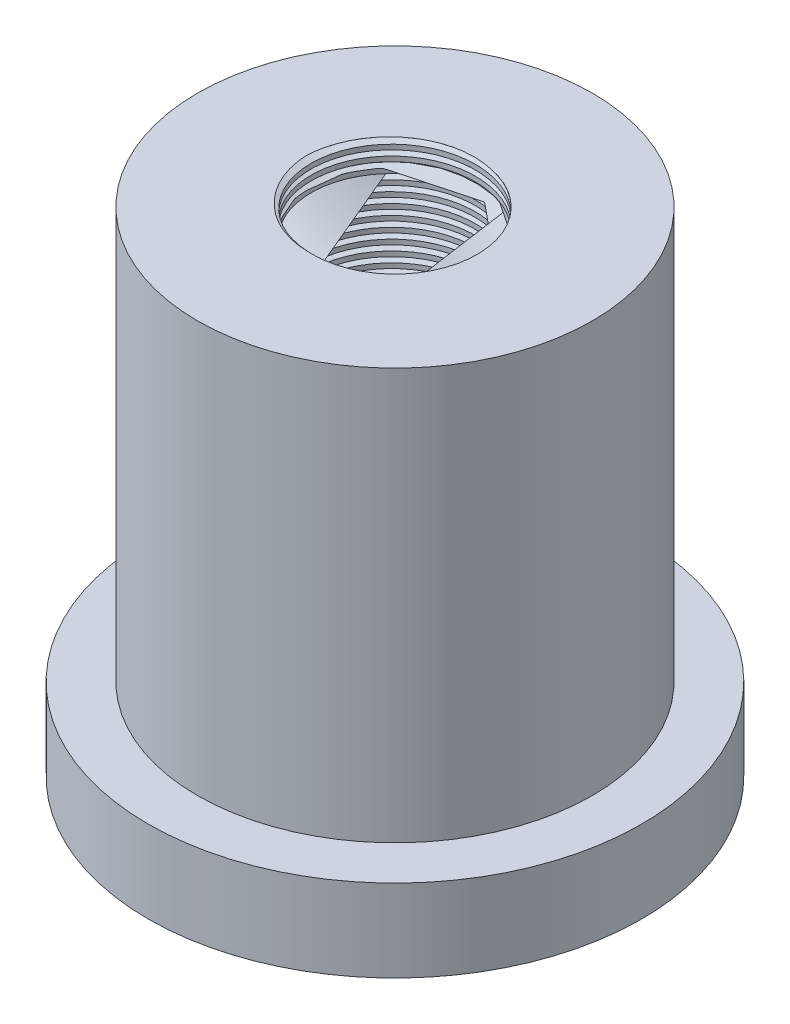
SolidWorks part; units mm, degrees
ref_plane "Front Plane" through (0, 0, 0) normal (0, 0, 1) x (1, 0, 0)
ref_plane "Top Plane" through (0, 0, 0) normal (0, 1, 0) x (1, 0, 0)
ref_plane "Right Plane" through (0, 0, 0) normal (1, 0, 0) x (0, 0, -1)
sketch "Sketch1" plane through (0, 0, 0) normal (0, 1, 0) x (1, 0, 0)
  circle A0 centre (0, 0) radius 6
  dimension "D1" = 12
extrude "Boss-Extrude6" add sketch "Sketch1" along normal blind 2
sketch "Sketch4" plane through (0, 2, 0) normal (0, 1, 0) x (1, 0, 0)
  circle A0 centre (0, 0) radius 4.8
  dimension "D1" = 9.6
extrude "Boss-Extrude7" add sketch "Sketch4" along normal blind 10
sketch "Sketch5" plane through (0, 12, 0) normal (0, 1, 0) x (1, 0, 0)
  circle A0 centre (0, 0) radius 2
  dimension "D1" = 4
extrude "Cut-Extrude1" cut sketch "Sketch5" against normal blind 12
sketch "Sketch6" plane through (0, 12, 0) normal (0, 1, 0) x (1, 0, 0)
  circle A0 centre (0, 0) radius 2
curve "Helix/Spiral1" pitch 0.25 height 10 radius 2 centre (0, 12, 0) axis (0, -1, 0) start towards (0, 0, 1)
sketch "Sketch10" plane through (0, 0, 0) normal (0, 1, 0) x (1, 0, 0)
  line L0 (-1.9333, -0.434) -> (-1.7606, -0.3241)
  line L1 (-1.7606, -0.3241) -> (-1.7606, -0.544)
  line L2 (-1.7606, -0.544) -> (-1.9333, -0.434)
sketch "Sketch12" plane through (0, 0, 0) normal (0, 0, 1) x (1, 0, 0)
  line L0 (-2.1618, 12) -> (-1.8316, 12.1432)
  line L1 (4.8, 12) -> (-4.8, 12) construction
  line L2 (-1.8316, 12.1432) -> (-1.8316, 11.8783)
  line L3 (-1.8316, 11.8783) -> (-2.1618, 12)
  point P1 (-1.8316, 11.8783)
  point P5 (-2.1618, 12)
  point P6 (0, 0)
  point P7 (0, 0)
sweep "Cut-Sweep3" cut profiles "Sketch12" path "Helix/Spiral1" align with end faces yes
